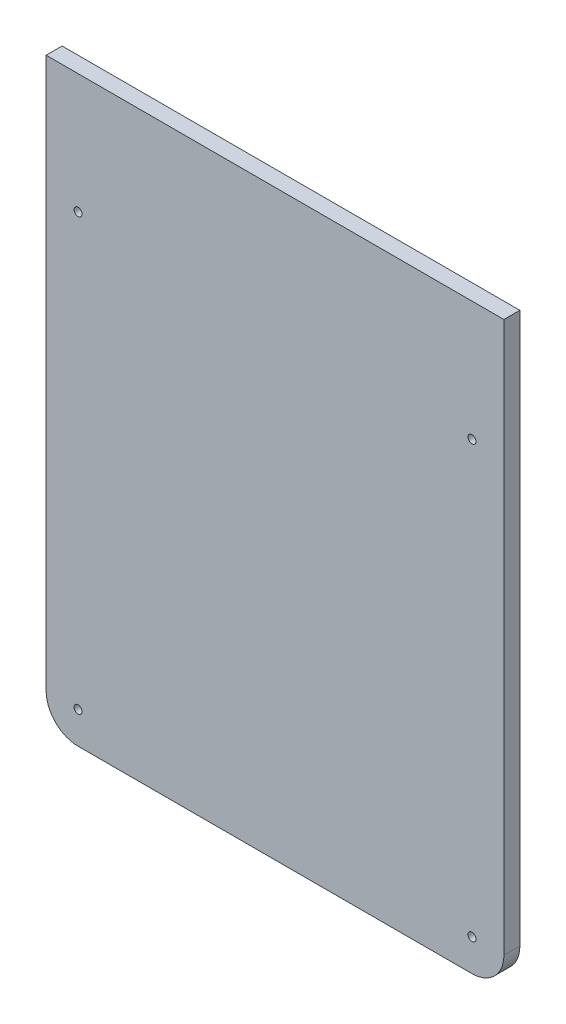
SolidWorks part; units mm, degrees
material "Beech"
ref_plane "Front Plane" through (0, 0, 0) normal (0, 0, 1) x (1, 0, 0)
ref_plane "Top Plane" through (0, 0, 0) normal (0, 1, 0) x (1, 0, 0)
ref_plane "Right Plane" through (0, 0, 0) normal (1, 0, 0) x (0, 0, -1)
sketch "Sketch1" plane through (0, 0, 0) normal (0, 0, 1) x (1, 0, 0)
  line L0 (-19.05, 903.0272) -> (-19.05, 155.124) construction
  line L1 (163.1, 903.0272) -> (163.1, 155.124) construction
  line L2 (-19.05, 903.0272) -> (163.1, 903.0272)
  line L3 (0, 903.0272) -> (19.05, 903.0272) construction
  line L4 (-6.35, 671.2522) -> (150.4, 671.2522) construction
  line L5 (163.1, 683.9522) -> (163.1, 855.4022) construction
  line L6 (-6.35, 671.2522) -> (150.4, 671.2522)
  line L7 (163.1, 683.9522) -> (163.1, 903.0272)
  line L10 (-19.05, 903.0272) -> (-19.05, 683.9522)
  arc A0 (-19.05, 683.9522) -> (-6.35, 671.2522) centre (-6.35, 683.9522) ccw construction
  arc A1 (150.4, 671.2522) -> (163.1, 683.9522) centre (150.4, 683.9522) ccw construction
  arc A2 (-19.05, 683.9522) -> (-6.35, 671.2522) centre (-6.35, 683.9522) ccw
  arc A3 (150.4, 671.2522) -> (163.1, 683.9522) centre (150.4, 683.9522) ccw
extrude "Boss-Extrude1" add sketch "Sketch1" along normal blind 6.35
hole_wizard "Hole1" positions "Sketch2" profile "Sketch3" legacy
sketch "Sketch2" plane through (72.025, -437.637, 19.05) normal (0, 0, 1) x (1, 0, 0)
  point P0 (-78.375, 1293.0392)
  point P3 (-78.375, 1121.5892)
  point P6 (78.375, 1121.5892)
  point P9 (78.375, 1293.0392)
sketch "Sketch3" plane through (-6.35, 855.4022, 19.05) normal (1, 0, 0) x (0, -1, 0)
  line L0 (0, 0) -> (0, 32.7039)
  line L1 (0, 32.7039) -> (1.5875, 31.75)
  line L2 (1.5875, 31.75) -> (1.5875, 4.0177)
  line L3 (1.5875, 4.0177) -> (5.08, 0)
  line L4 (5.08, 0) -> (0, 0)
  line L5 (0, -14.3089) -> (0, 102.4216) construction
  line L6 (0, 32.7039) -> (-1.5875, 31.75) construction
  line L7 (-1.5875, 4.0177) -> (-5.08, 0) construction
  dimension "Diameter" = 3.175
  dimension "Depth" = 31.75
  dimension "C-Sink Diameter" = 10.16
  dimension "C-Sink Angle" = 82
  dimension "Drill Angle" = 118
